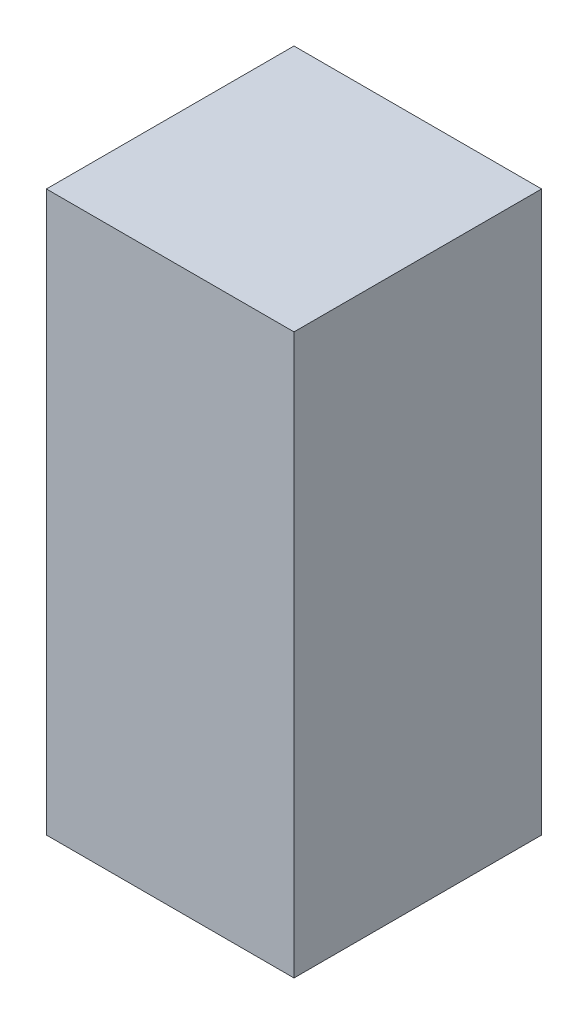
SolidWorks part; units mm, degrees
ref_plane "Alzado" through (0, 0, 0) normal (0, 0, 1) x (1, 0, 0)
ref_plane "Planta" through (0, 0, 0) normal (0, 1, 0) x (1, 0, 0)
ref_plane "Vista lateral" through (0, 0, 0) normal (1, 0, 0) x (0, 0, -1)
sketch "Sketch1" plane through (0, 0, 0) normal (0, 1, 0) x (1, 0, 0)
  line L1 (-50, 50) -> (50, 50)
  line L2 (-50, 50) -> (-50, -50)
  line L3 (-50, -50) -> (50, -50)
  line L4 (50, 50) -> (50, -50)
  line L5 (-50, 50) -> (50, -50) construction
  line L6 (-50, -50) -> (50, 50) construction
  point P0 (0, 0)
  dimension "D1" = 100
  dimension "D2" = 100
extrude "Boss-Extrude1" add sketch "Sketch1" along normal blind 226
